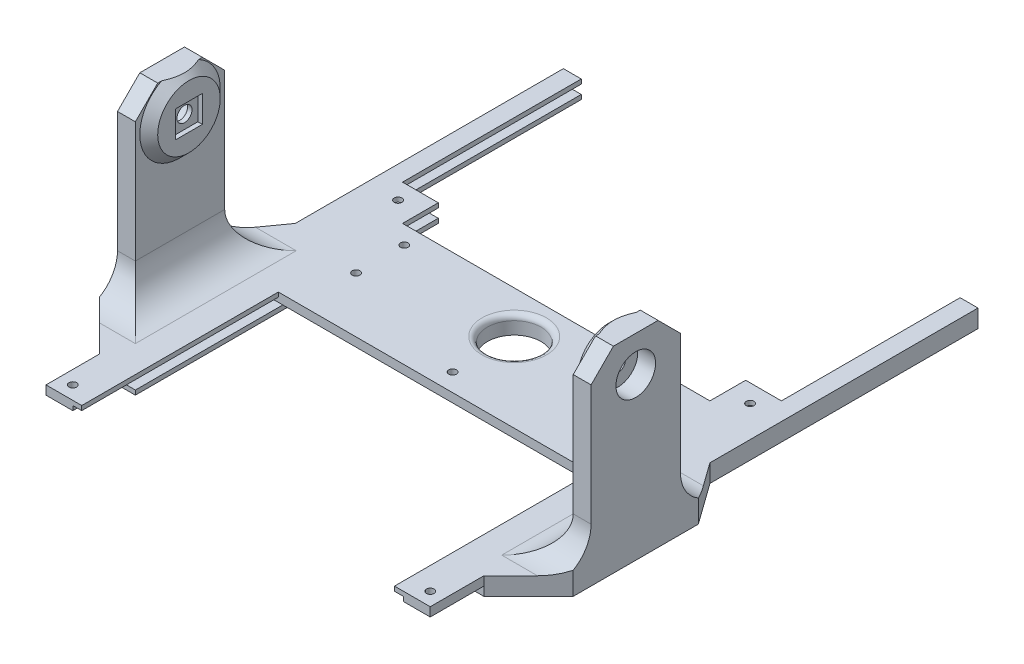
SolidWorks part; units mm, degrees
ref_plane "Alzado" through (0, 0, 0) normal (0, 0, 1) x (1, 0, 0)
ref_plane "Planta" through (0, 0, 0) normal (0, 1, 0) x (1, 0, 0)
ref_plane "Vista lateral" through (0, 0, 0) normal (1, 0, 0) x (0, 0, -1)
sketch "Croquis1" plane through (0, 0, 0) normal (0, 1, 0) x (1, 0, 0)
  line L0 (116, 58) -> (132.5, 35)
  line L8 (116, 88) -> (116, 58)
  line L12 (-132.5, 35) -> (-132.5, -35)
  line L18 (-107.5, -60) -> (-132.5, -35)
  line L22 (-116, 88) -> (-116, 58)
  line L23 (-116, 58) -> (-132.5, 35)
  line L552 (107.5, -60) -> (132.5, -35)
  line L553 (132.5, 35) -> (132.5, -35)
  line L554 (0, 0) -> (0, -155) construction
  line L558 (-80, -60) -> (0, -60) construction
  line L559 (0, -60) -> (80, -60) construction
  line L566 (-132.5, 0) -> (0, 0) construction
  line L567 (0, 0) -> (132.5, 0) construction
  line L569 (0, 101) -> (0, 0) construction
  line L570 (-116, 88) -> (116, 88)
  line L572 (-92.5, -90) -> (-92.5, 40)
  line L573 (-92.5, 40) -> (92.5, 40)
  line L574 (92.5, 40) -> (92.5, -90)
  line L577 (-107.5, -60) -> (-107.5, -90)
  line L578 (-107.5, -90) -> (-92.5, -90)
  line L579 (107.5, -60) -> (107.5, -90)
  line L580 (107.5, -90) -> (92.5, -90)
  point P16 (-132.5, 0)
  dimension "D8" = 25
  dimension "D2" = 232
  dimension "D4" = 30
  dimension "D5" = 30
  dimension "D6" = 130
  dimension "D7" = 23
  dimension "D9" = 25
  dimension "D10" = 15
  dimension "D16" = 265
  dimension "D30" = 70
extrude "Saliente-Extruir2" add sketch "Croquis1" along normal blind 10
sketch "Croquis3" plane through (0, 10, 0) normal (0, 1, 0) x (1, 0, 0)
  line L0 (132.5, 25) -> (122.5, 25)
  line L1 (132.5, -35) -> (132.5, 35) construction
  line L2 (122.5, 25) -> (122.5, -25)
  line L3 (122.5, -25) -> (132.5, -25)
  line L4 (132.5, -25) -> (132.5, 25)
  line L5 (132.5, 35) -> (132.5, 25) construction
  line L6 (132.5, -25) -> (132.5, -35) construction
  line L7 (0, -155) -> (0, -12.7186) construction
  line L10 (0, -135.114) -> (0, 15) construction
  line L11 (0, 64.5) -> (0, -38.3443) construction
  line L12 (-122.5, -25) -> (-132.5, -25)
  line L13 (-122.5, 25) -> (-122.5, -25)
  line L14 (-132.5, 25) -> (-122.5, 25)
  line L15 (-132.5, -25) -> (-132.5, 25)
  dimension "D1" = 10
  dimension "D2" = 50
extrude "Saliente-Extruir4" add sketch "Croquis3" along normal blind 100
sketch "Croquis4" plane through (132.5, 0, 0) normal (1, 0, 0) x (0, 0, -1)
  line L0 (0, 110) -> (0, 90) construction
  line L1 (-25, 110) -> (25, 110) construction
  circle A0 centre (0, 90) radius 11.1
  dimension "D1" = 22.2
  dimension "D2" = 20
extrude "Cortar-Extruir1" cut sketch "Croquis4" against normal through all both and the other way through all
sketch "Croquis5" plane through (122.5, 0, 0) normal (-1, 0, 0) x (0, 0, 1)
  circle A0 centre (0, 90) radius 17.5
  circle A1 centre (0, 90) radius 4.2
  dimension "D1" = 8.4
  dimension "D2" = 35
extrude "Saliente-Extruir5" add sketch "Croquis5" along normal blind 5
chamfer "Chaflán1" distance 5 angle 45 1 edges at (122.5, 90, -17.5)
sketch "Croquis6" plane through (-122.5, 0, 0) normal (1, 0, 0) x (0, 0, -1)
  circle A0 centre (0, 90) radius 4.2
  circle A1 centre (0, 90) radius 17.5
  dimension "D1" = 35
  dimension "D2" = 8.4
extrude "Saliente-Extruir6" add sketch "Croquis6" along normal blind 5
chamfer "Chaflán3" distance 12.5 angle 45 4 edges at (-127.5, 110, -25) (-127.5, 110, 25) (127.5, 110, -25) (127.5, 110, 25)
chamfer "Chaflán2" distance 5 angle 45 1 edges at (-122.5, 90, 17.5)
sketch "Croquis8" plane through (-117.5, 0, 0) normal (1, 0, 0) x (0, 0, -1)
  line L1 (-7.5, 97.5) -> (7.5, 97.5)
  line L2 (-7.5, 97.5) -> (-7.5, 82.5)
  line L3 (-7.5, 82.5) -> (7.5, 82.5)
  line L4 (7.5, 97.5) -> (7.5, 82.5)
  line L5 (-7.5, 97.5) -> (7.5, 82.5) construction
  line L6 (-7.5, 82.5) -> (7.5, 97.5) construction
  circle A0 centre (0, 90) radius 4.2
  dimension "D2" = 8.4
  dimension "D1" = 15
extrude "Cortar-Extruir3" cut sketch "Croquis8" against normal blind 2.5
fillet "Redondeo1" radius 20 6 edges at (-127.5, 10, -25) (-127.5, 10, 25) (-122.5, 10, 0) (122.5, 10, 0) (127.5, 10, -25) (127.5, 10, 25)
sketch "Croquis14" plane through (0, 0, -88) normal (0, 0, -1) x (-1, 0, 0)
  line L0 (-86, 10) -> (-116, 10)
  line L1 (-116, 10) -> (-116, 0)
  line L2 (-116, 0) -> (-86, 0)
  line L3 (-116, 0) -> (116, 0) construction
  line L4 (-86, 0) -> (-86, 2.5)
  line L5 (-86, 2.5) -> (-111, 2.5)
  line L6 (-111, 2.5) -> (-111, 7.5)
  line L7 (-111, 7.5) -> (-86, 7.5)
  line L8 (-86, 7.5) -> (-86, 10)
  line L9 (0, 0) -> (0, 10) construction
  line L10 (-116, 10) -> (116, 10) construction
  line L11 (111, 7.5) -> (86, 7.5)
  line L12 (111, 2.5) -> (111, 7.5)
  line L13 (86, 2.5) -> (111, 2.5)
  line L14 (86, 0) -> (86, 2.5)
  line L15 (116, 0) -> (86, 0)
  line L16 (116, 10) -> (116, 0)
  line L17 (86, 10) -> (116, 10)
  line L18 (86, 7.5) -> (86, 10)
  dimension "D1" = 30
  dimension "D2" = 5
  dimension "D3" = 2.5
extrude "Saliente-Extruir9" add sketch "Croquis14" along normal blind 20
sketch "Croquis7" plane through (117.5, 0, 0) normal (-1, 0, 0) x (0, 0, 1)
  line L1 (-7.5, 97.5) -> (7.5, 97.5)
  line L2 (-7.5, 97.5) -> (-7.5, 82.5)
  line L3 (-7.5, 82.5) -> (7.5, 82.5)
  line L4 (7.5, 97.5) -> (7.5, 82.5)
  line L5 (-7.5, 97.5) -> (7.5, 82.5) construction
  line L6 (-7.5, 82.5) -> (7.5, 97.5) construction
  circle A0 centre (0, 90) radius 4.2
  dimension "D2" = 8.4
  dimension "D1" = 15
extrude "Cortar-Extruir2" cut sketch "Croquis7" against normal blind 2.5
sketch "Croquis9" plane through (0, 10, 0) normal (0, 1, 0) x (1, 0, 0)
  line L0 (0, 0) -> (0, 64.5) construction
  line L1 (0, 64.5) -> (0, 88) construction
  line L2 (86, 88) -> (-86, 88) construction
  line L3 (0, 78) -> (-75, 78) construction
  line L4 (-75, 78) -> (-75, 88) construction
  line L5 (0, 64.5) -> (-49.1848, 64.5) construction
  line L6 (100, -90) -> (100, -75) construction
  line L7 (92.5, -90) -> (107.5, -90) construction
  line L8 (86, 98) -> (111, 98) construction
  line L9 (86, 108) -> (86, 88) construction
  circle A0 centre (0, 64.5) radius 15
  circle A1 centre (-75, 78) radius 2.15
  circle A2 centre (75, 78) radius 2.15
  circle A3 centre (75, 51) radius 2.15
  circle A4 centre (-75, 51) radius 2.15
  circle A5 centre (100, -82.5) radius 2.15
  circle A6 centre (-100, -82.5) radius 2.15
  circle A7 centre (98.5, 98) radius 2.15
  circle A8 centre (-98.5, 98) radius 2.15
  dimension "D3" = 30
  dimension "D6" = 4.3
  dimension "D8" = 4.3
  dimension "D10" = 4.3
  dimension "D1" = 64.5
  dimension "D2" = 23.5
  dimension "D4" = 13.5
  dimension "D5" = 75
  dimension "D7" = 15
  dimension "D9" = 25
extrude "Cortar-Extruir4" cut sketch "Croquis9" against normal blind 10
fillet "Redondeo2" radius 3 1 edges at (0, 10, -49.5)
sketch "Croquis11" plane through (0, 10, 0) normal (0, 1, 0) x (1, 0, 0)
  line L1 (-92.5, 40) -> (92.5, 40)
  line L8 (-92.5, 40) -> (-92.5, 20)
  line L9 (-92.5, -90) -> (-92.5, 40) construction
  line L10 (-92.5, 20) -> (92.5, 20)
  line L11 (92.5, 40) -> (92.5, -90) construction
  line L12 (92.5, 20) -> (92.5, 40)
  line L13 (0, 20) -> (0, 40) construction
  circle A0 centre (0, 30) radius 2.15
  dimension "D2" = 4.3
  dimension "D1" = 20
extrude "Saliente-Extruir7" add sketch "Croquis11" against normal blind 5
sketch "Croquis12" plane through (0, 0, 90) normal (0, 0, 1) x (1, 0, 0)
  line L0 (-92.5, 10) -> (-87.5, 10)
  line L1 (-92.5, 10) -> (92.5, 10) construction
  line L2 (-87.5, 10) -> (-87.5, 7.5)
  line L3 (-87.5, 7.5) -> (-92.5, 7.5)
  line L4 (-92.5, 5) -> (-92.5, 10) construction
  line L5 (-92.5, 7.5) -> (-92.5, 5) construction
  line L6 (-92.5, 10) -> (-92.5, 0) construction
  line L7 (-92.5, 2.5) -> (-87.5, 2.5)
  line L8 (-87.5, 2.5) -> (-87.5, 0)
  line L9 (-92.5, 0) -> (92.5, 0) construction
  line L10 (-87.5, 0) -> (-92.5, 0)
  line L11 (-92.5, 0) -> (-92.5, 2.5)
  line L12 (-92.5, 5) -> (-92.5, 2.5) construction
  line L13 (-92.5, 10) -> (-92.5, 7.5)
  line L14 (0, 0) -> (0, 23.8317) construction
  line L15 (92.5, 0) -> (92.5, 2.5)
  line L16 (87.5, 0) -> (92.5, 0)
  line L17 (87.5, 2.5) -> (87.5, 0)
  line L18 (92.5, 2.5) -> (87.5, 2.5)
  line L19 (92.5, 10) -> (87.5, 10)
  line L20 (87.5, 10) -> (87.5, 7.5)
  line L21 (87.5, 7.5) -> (92.5, 7.5)
  line L22 (92.5, 10) -> (92.5, 7.5)
  dimension "D1" = 2.5
  dimension "D2" = 5
extrude "Saliente-Extruir8" add sketch "Croquis12" against normal up to surface (130 mm away) up to face at (0, 2.5, -40)
sketch "Croquis13" plane through (0, 0, 90) normal (0, 0, 1) x (1, 0, 0)
  line L0 (-92.5, 5) -> (-107.5, 5)
  line L1 (-92.5, 7.5) -> (-92.5, 2.5) construction
  line L2 (-107.5, 10) -> (-107.5, 0) construction
  line L3 (-107.5, 5) -> (-107.5, 0)
  line L4 (-107.5, 0) -> (-87.5, 0)
  line L5 (-87.5, 0) -> (-87.5, 5)
  line L6 (-92.5, 5) -> (92.5, 5) construction
  line L7 (-87.5, 5) -> (-92.5, 5)
  line L8 (0, 0) -> (0, 28.3473) construction
  line L9 (87.5, 0) -> (87.5, 5)
  line L10 (107.5, 0) -> (87.5, 0)
  line L11 (107.5, 5) -> (107.5, 0)
  line L12 (92.5, 5) -> (107.5, 5)
  line L13 (87.5, 5) -> (92.5, 5)
extrude "Cortar-Extruir5" cut sketch "Croquis13" against normal blind 30
sketch "Croquis15" plane through (0, 0, -108) normal (0, 0, -1) x (-1, 0, 0)
  line L0 (-106, 2.5) -> (-111, 2.5)
  line L1 (-86, 2.5) -> (-111, 2.5) construction
  line L2 (-111, 2.5) -> (-111, 7.5)
  line L3 (-111, 7.5) -> (-106, 7.5)
  line L4 (-111, 7.5) -> (-86, 7.5) construction
  line L5 (-106, 7.5) -> (-106, 10)
  line L6 (-86, 10) -> (-116, 10) construction
  line L7 (-106, 10) -> (-116, 10)
  line L8 (-116, 10) -> (-116, 0)
  line L9 (-116, 0) -> (-106, 0)
  line L10 (-116, 0) -> (-86, 0) construction
  line L11 (-106, 0) -> (-106, 2.5)
  line L12 (0, 0) -> (0, 6.7597) construction
  line L13 (116, 0) -> (106, 0)
  line L14 (116, 10) -> (116, 0)
  line L15 (106, 10) -> (116, 10)
  line L16 (106, 7.5) -> (106, 10)
  line L17 (111, 7.5) -> (106, 7.5)
  line L18 (111, 2.5) -> (111, 7.5)
  line L19 (106, 2.5) -> (111, 2.5)
  line L20 (106, 0) -> (106, 2.5)
  dimension "D1" = 5
  dimension "D2" = 5
extrude "Saliente-Extruir10" add sketch "Croquis15" along normal blind 100
